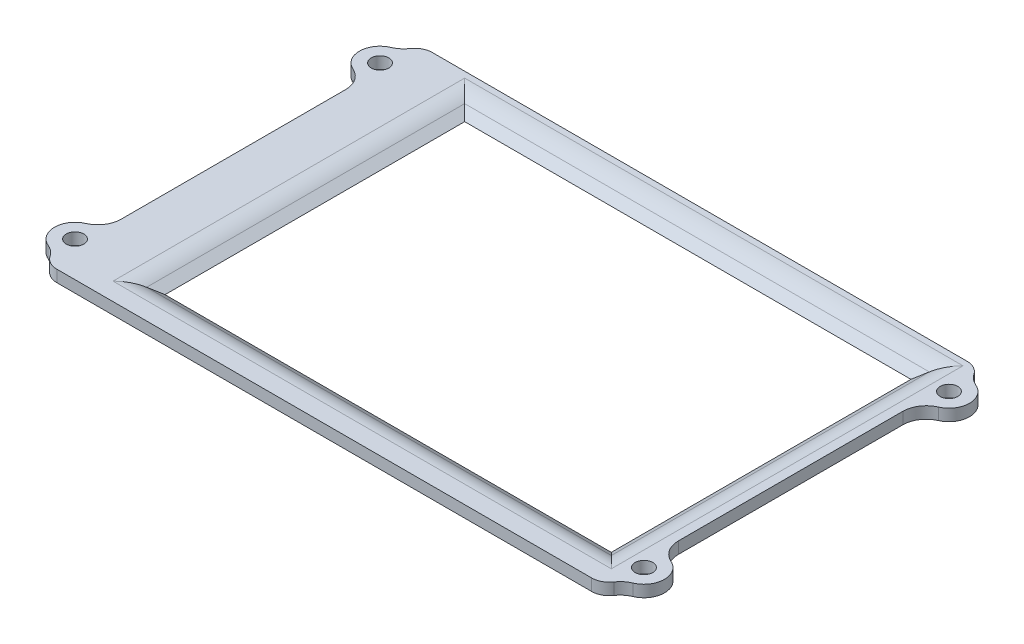
SolidWorks part; units mm, degrees
ref_plane "Front Plane" through (0, 0, 0) normal (0, 0, 1) x (1, 0, 0)
ref_plane "Top Plane" through (0, 0, 0) normal (0, 1, 0) x (1, 0, 0)
ref_plane "Right Plane" through (0, 0, 0) normal (1, 0, 0) x (0, 0, -1)
sketch "Sketch1" plane through (0, 0, 0) normal (0, 1, 0) x (1, 0, 0)
  line L1 (47.5, -32) -> (-47.5, -32)
  line L2 (47.5, -32) -> (47.5, 32)
  line L3 (47.5, 32) -> (-47.5, 32)
  line L4 (-47.5, -32) -> (-47.5, 32)
  line L5 (47.5, -32) -> (-47.5, 32) construction
  line L6 (47.5, 32) -> (-47.5, -32) construction
  point P0 (0, 0)
  dimension "D1" = 64
  dimension "D2" = 95
extrude "Boss-Extrude1" add sketch "Sketch1" along normal blind 2
sketch "Sketch2" plane through (0, 2, 0) normal (0, 1, 0) x (1, 0, 0)
  circle A0 centre (-48.5, -26) radius 3.5
  circle A1 centre (-48.5, 26) radius 3.5
  circle A2 centre (48.5, -26) radius 3.5
  circle A3 centre (48.5, 26) radius 3.5
  dimension "D1" = 7
extrude "Boss-Extrude2" add sketch "Sketch2" against normal up to surface (2 mm away) up to face at (0, 0, 0)
fillet "Fillet1" radius 4 8 edges at (-47.5, 1, 22.6459) (-47.5, 1, 29.3541) (-47.5, 1, -22.6459) (-47.5, 1, -29.3541) (47.5, 1, -22.6459) (47.5, 1, -29.3541) (47.5, 1, 22.6459) (47.5, 1, 29.3541)
fillet "Fillet2" radius 3 4 edges at (47.5, 1, -32) (47.5, 1, 32) (-47.5, 1, 32) (-47.5, 1, -32)
sketch "Sketch3" plane through (0, 2, 0) normal (0, 1, 0) x (1, 0, 0)
  circle A0 centre (48.5, -26) radius 1.5
  circle A1 centre (48.5, 26) radius 1.5
  circle A2 centre (-48.5, 26) radius 1.5
  circle A3 centre (-48.5, -26) radius 1.5
  dimension "D1" = 3
extrude "Cut-Extrude1" cut sketch "Sketch3" against normal through all
sketch "Sketch4" plane through (0, 2, 0) normal (0, 1, 0) x (1, 0, 0)
  line L1 (-34.4709, -24.3983) -> (41.3291, -24.3983)
  line L2 (-34.4709, -24.3983) -> (-34.4709, 26.4017)
  line L3 (-34.4709, 26.4017) -> (41.3291, 26.4017)
  line L4 (41.3291, -24.3983) -> (41.3291, 26.4017)
extrude "Cut-Extrude2" cut sketch "Sketch4" against normal through all
chamfer "Chamfer1" distance 3 angle 35 4 edges at (-34.4709, 2, -1.0017) (3.4291, 2, -26.4017) (41.3291, 2, -1.0017) (3.4291, 2, 24.3983) first distance on face at (3.4291, 2, -1.0017)
fillet "Fillet3" radius 5 4 edges at (44.3291, 2, -1.0017) (3.4291, 2, -29.4017) (-37.4709, 2, -1.0017) (3.4291, 2, 27.3983)
